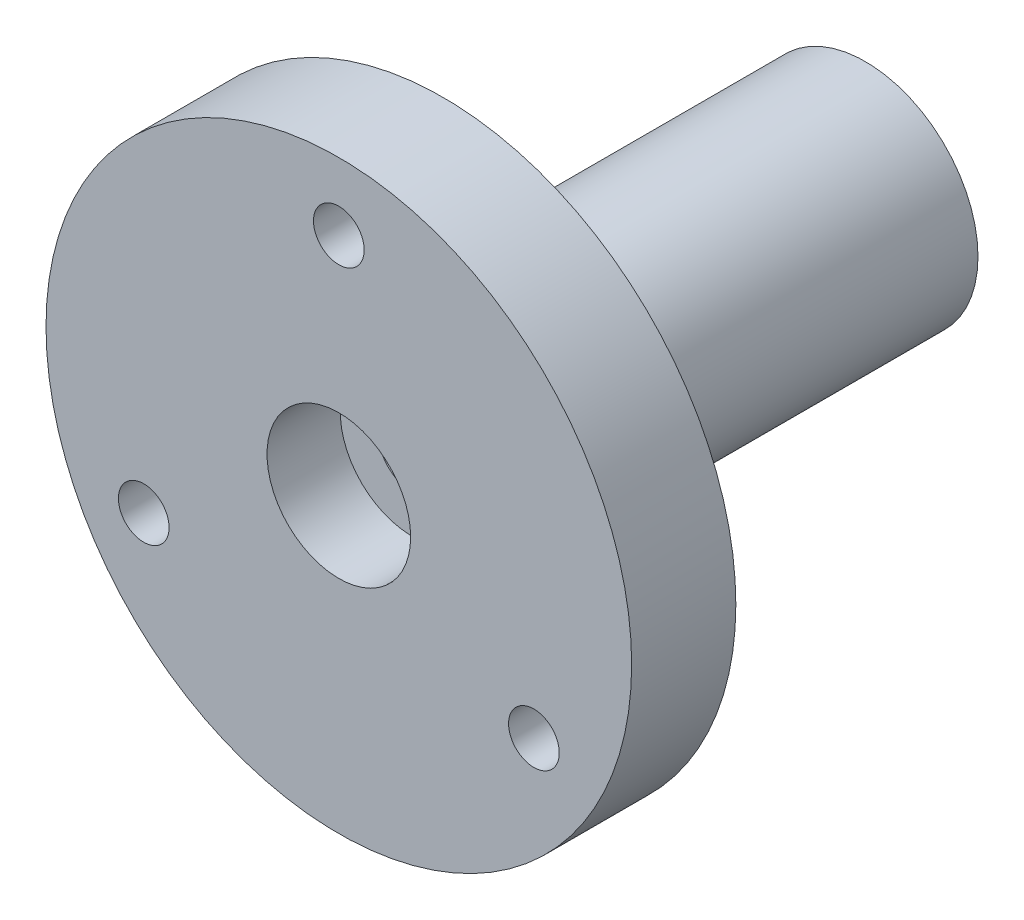
SolidWorks part; units mm, degrees
ref_plane "前视基准面" through (0, 0, 0) normal (0, 0, 1) x (1, 0, 0)
ref_plane "上视基准面" through (0, 0, 0) normal (0, 1, 0) x (1, 0, 0)
ref_plane "右视基准面" through (0, 0, 0) normal (1, 0, 0) x (0, 0, -1)
other "Configuration Table"
sketch "草图1" plane through (0, 0, 0) normal (0, 0, 1) x (1, 0, 0)
  circle A0 centre (0, 0) radius 10.4
  dimension "D1" = 20.8
extrude "凸台-拉伸1" add sketch "草图1" along normal blind 3.7 contours A0
sketch "草图2" plane through (0, 0, 0) normal (0, 0, -1) x (-1, 0, 0)
  circle A0 centre (0, 8) radius 1.5
  circle A1 centre (0, 8) radius 0.9
  dimension "D1" = 3
  dimension "D2" = 1.8
  dimension "D3" = 8
extrude "切除-拉伸1" cut sketch "草图2" against normal through all contours A1
extrude "切除-拉伸2" cut sketch "草图2<3>" against normal blind 1.5 contours A0
sketch "草图2<3>" plane through (0, 0, 0) normal (0, 0, -1) x (-1, 0, 0) same geometry as "草图2"
pattern_circular "阵列(圆周)1" count 3 over 360 about axis through (0, 0, 3.7) along (0, 0, -1) of "切除-拉伸1", "切除-拉伸2" reverse direction yes
sketch "草图3" plane through (0, 0, 0) normal (0, 0, -1) x (-1, 0, 0)
  circle A0 centre (0, 0) radius 2.55
  circle A1 centre (0, 0) radius 1.2
  dimension "D1" = 2.4
  dimension "D2" = 5.1
extrude "切除-拉伸3" cut sketch "草图3" against normal through all contours A1
sketch "草图4" plane through (0, 0, 3.7) normal (0, 0, 1) x (1, 0, 0)
  circle A1 centre (0, 0) radius 2.55
  dimension "D1" = 5.1
extrude "切除-拉伸4" cut sketch "草图4" against normal blind 2.6
sketch "草图5" plane through (0, 0, 0) normal (0, 0, -1) x (-1, 0, 0)
  circle A0 centre (0, 0) radius 1.2
  circle A1 centre (0, 0) radius 4
  circle A2 centre (0, 0) radius 1.2 construction
  dimension "D1" = 2.4
  dimension "D2" = 8
extrude "凸台-拉伸2" add sketch "草图5" along normal blind 15
